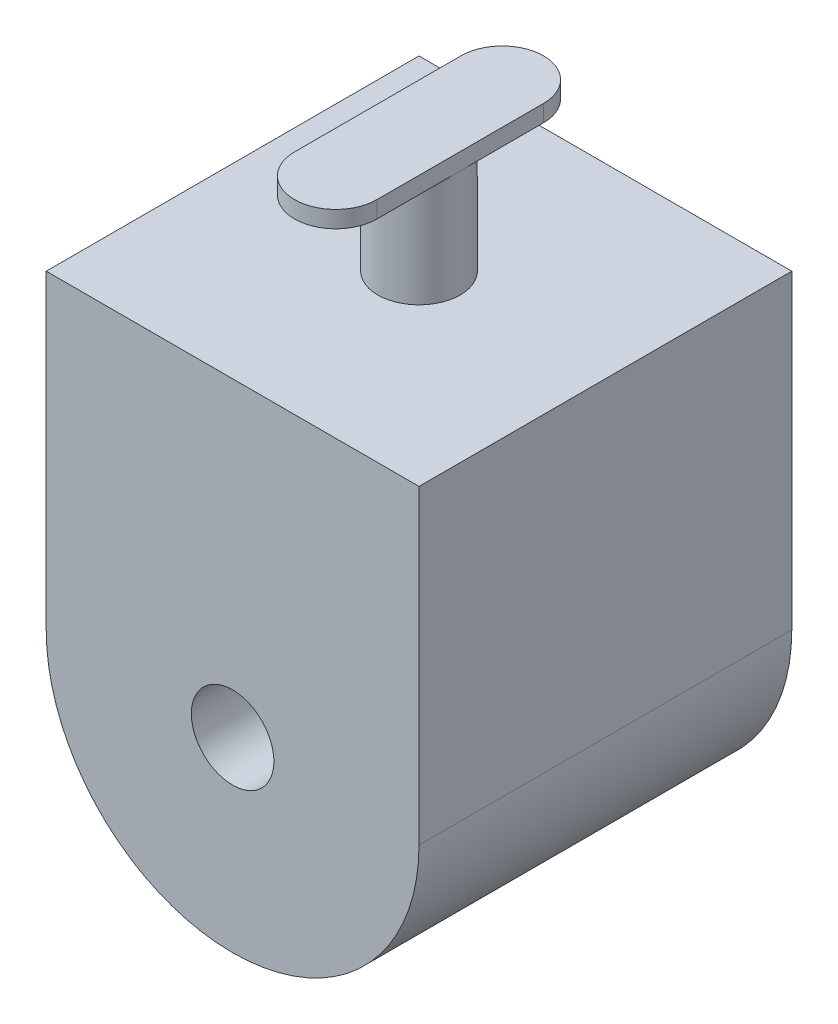
SolidWorks part; units mm, degrees
ref_plane "Front Plane" through (0, 0, 0) normal (0, 0, 1) x (1, 0, 0)
ref_plane "Top Plane" through (0, 0, 0) normal (0, 1, 0) x (1, 0, 0)
ref_plane "Right Plane" through (0, 0, 0) normal (1, 0, 0) x (0, 0, -1)
sketch "Sketch1" plane through (0, 0, 0) normal (0, 0, 1) x (1, 0, 0)
  line L2 (-19.05, -15.875) -> (-19.05, 15.875)
  line L3 (-19.05, 15.875) -> (19.05, 15.875)
  line L4 (19.05, -15.875) -> (19.05, 15.875)
  line L5 (-19.05, -15.875) -> (19.05, 15.875) construction
  line L6 (-19.05, 15.875) -> (19.05, -15.875) construction
  arc A0 (-19.05, -15.875) -> (19.05, -15.875) centre (0, -15.875) ccw
  point P0 (0, 0)
  dimension "D1" = 38.1
  dimension "D2" = 31.75
extrude "Boss-Extrude1" add sketch "Sketch1" along normal blind 38.1 contours L3 L4 A0 L2
sketch "Sketch2" plane through (0, 0, 0) normal (0, 0, -1) x (-1, 0, 0)
  circle A0 centre (0, -15.875) radius 4.2164
  dimension "D1" = 8.4328
extrude "Cut-Extrude1" cut sketch "Sketch2" against normal blind 38.1
sketch "Sketch3" plane through (0, 15.875, 0) normal (0, 1, 0) x (1, 0, 0)
  circle A0 centre (0, -19.05) radius 4.2164
  dimension "D1" = 8.4328
extrude "Boss-Extrude2" add sketch "Sketch3" along normal blind 12.7
sketch "Sketch4" plane through (0, 28.575, 0) normal (0, 1, 0) x (1, 0, 0)
  line L0 (0, -27.559) -> (0, -10.541) construction
  line L1 (-4.2164, -27.559) -> (-4.2164, -10.541)
  line L2 (4.2164, -27.559) -> (4.2164, -10.541)
  arc A0 (-4.2164, -27.559) -> (4.2164, -27.559) centre (0, -27.559) ccw
  arc A1 (4.2164, -10.541) -> (-4.2164, -10.541) centre (0, -10.541) ccw
  point P2 (0, -19.05)
  dimension "D1" = 17.018
  dimension "D2" = 8.4328
extrude "Boss-Extrude3" add sketch "Sketch4" against normal blind 1.7145
